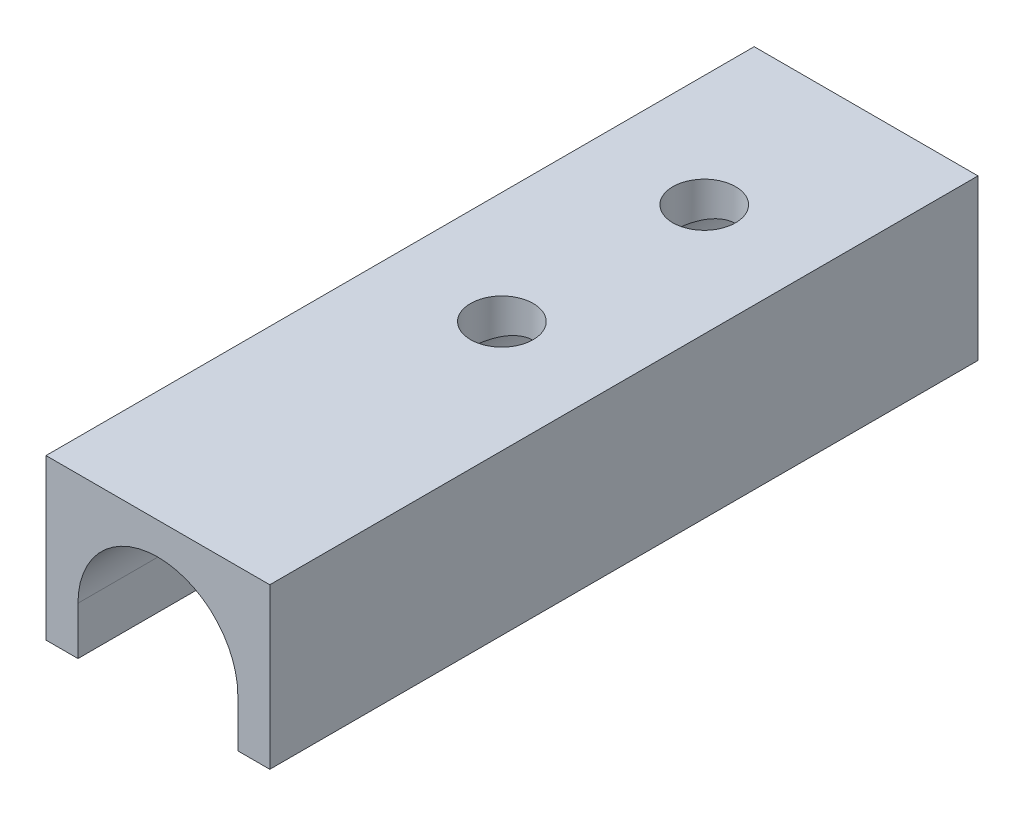
SolidWorks part; units mm, degrees
ref_plane "Front Plane" through (0, 0, 0) normal (0, 0, 1) x (1, 0, 0)
ref_plane "Top Plane" through (0, 0, 0) normal (0, 1, 0) x (1, 0, 0)
ref_plane "Right Plane" through (0, 0, 0) normal (1, 0, 0) x (0, 0, -1)
sketch "Sketch1" plane through (0, 0, 0) normal (0, 0, 1) x (1, 0, 0)
  line L0 (-5.53, 5.53) -> (5.53, 5.53)
  line L1 (-5.53, 5.53) -> (-5.53, -2.37)
  line L2 (5.53, 5.53) -> (5.53, -2.37)
  line L3 (3.95, -2.37) -> (3.95, 0)
  line L4 (5.53, -2.37) -> (3.95, -2.37)
  line L5 (-5.53, -2.37) -> (-3.95, -2.37)
  line L6 (-3.95, -2.37) -> (-3.95, 0)
  arc A0 (-3.95, 0) -> (3.95, 0) centre (0, 0) cw
  dimension "D1" = 3.95
  dimension "D3" = 5.53
  dimension "D4" = 7.9
  dimension "D2" = 11.06
extrude "Boss-Extrude1" add sketch "Sketch1" along normal mid plane 35
sketch "Sketch2" plane through (0, 5.53, 0) normal (0, 1, 0) x (1, 0, 0)
  line L0 (0, -44.7868) -> (0, 44.7868) construction
  line L1 (5.53, 17.5) -> (-5.53, 17.5) construction
  circle A0 centre (0, 9.5) radius 1.55
  circle A1 centre (0, -0.5) radius 1.55
  dimension "D3" = 3.1
  dimension "D1" = 10
  dimension "D2" = 8
extrude "Cut-Extrude1" cut sketch "Sketch2" against normal up to surface (1.58 mm away) up to face at (0, 1.975, 0)
equation "\"tubeRad\" = 3.95"
equation "\"D1@Sketch1\"=\"tubeRad\""
equation "\"D3@Sketch1\"=\"tubeRad\"+(\"tubeRad\"*2/5)"
equation "\"D4@Sketch1\"=\"tubeRad\"*2"
equation "\"MountHoleSize\"= 3.1"
equation "\"D3@Sketch2\"=\"MountHoleSize\""
equation "\"D2@Sketch1\"=\"tubeRad\"*2 +2*(\"tubeRad\"*2/5)"
